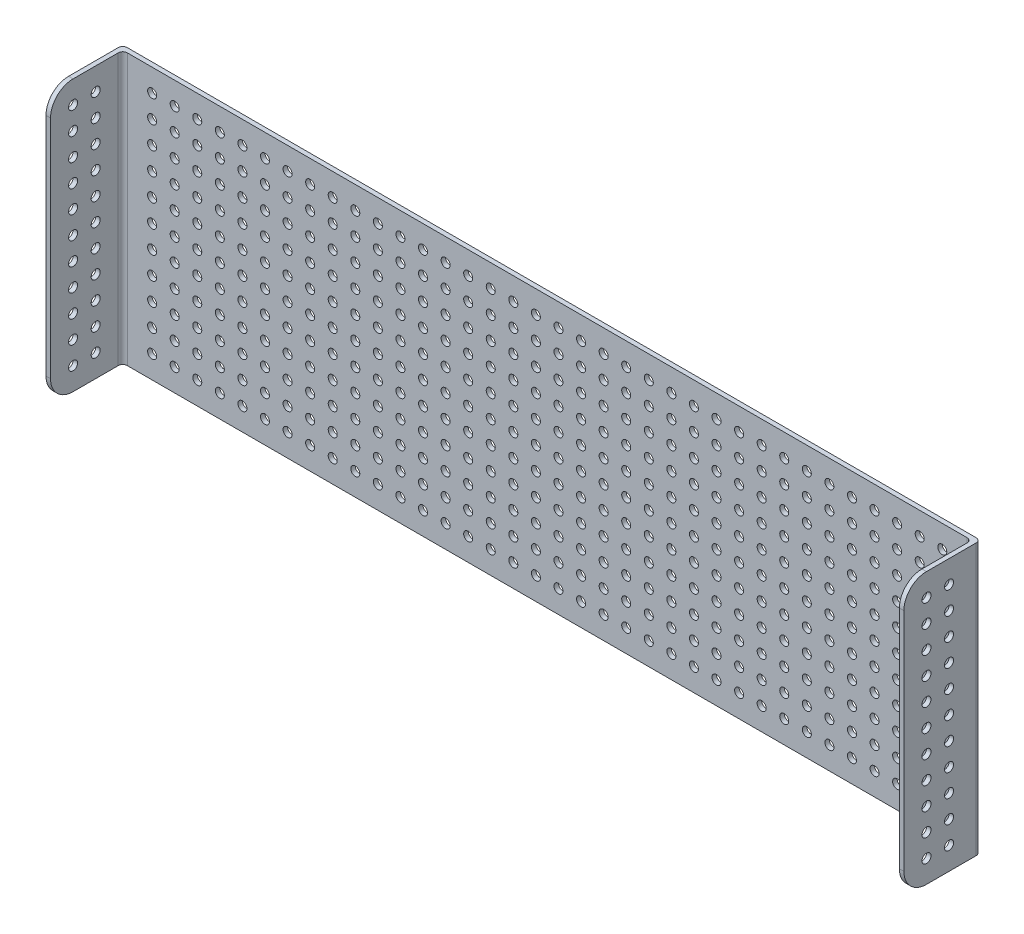
SolidWorks part; units mm, degrees
ref_plane "Front Plane" through (0, 0, 0) normal (0, 0, 1) x (1, 0, 0)
ref_plane "Top Plane" through (0, 0, 0) normal (0, 1, 0) x (1, 0, 0)
ref_plane "Right Plane" through (0, 0, 0) normal (1, 0, 0) x (0, 0, -1)
sketch "Çizim1" plane through (0, 0, 0) normal (0, 0, 1) x (1, 0, 0)
  line L1 (-65.3318, 26.6587) -> (314.6682, 26.6587)
  line L2 (-65.3318, 26.6587) -> (-65.3318, -93.3413)
  line L3 (-65.3318, -93.3413) -> (314.6682, -93.3413)
  line L4 (314.6682, 26.6587) -> (314.6682, -93.3413)
  circle A0 centre (299.6682, 16.6587) radius 2
  circle A1 centre (289.6682, 16.6587) radius 2
  circle A2 centre (279.6682, 16.6587) radius 2
  circle A3 centre (269.6682, 16.6587) radius 2
  circle A4 centre (259.6682, 16.6587) radius 2
  circle A5 centre (249.6682, 16.6587) radius 2
  circle A6 centre (239.6682, 16.6587) radius 2
  circle A7 centre (229.6682, 16.6587) radius 2
  circle A8 centre (219.6682, 16.6587) radius 2
  circle A9 centre (209.6682, 16.6587) radius 2
  circle A10 centre (199.6682, 16.6587) radius 2
  circle A11 centre (189.6682, 16.6587) radius 2
  circle A12 centre (179.6682, 16.6587) radius 2
  circle A13 centre (169.6682, 16.6587) radius 2
  circle A14 centre (159.6682, 16.6587) radius 2
  circle A15 centre (149.6682, 16.6587) radius 2
  circle A16 centre (139.6682, 16.6587) radius 2
  circle A17 centre (129.6682, 16.6587) radius 2
  circle A18 centre (119.6682, 16.6587) radius 2
  circle A19 centre (109.6682, 16.6587) radius 2
  circle A20 centre (99.6682, 16.6587) radius 2
  circle A21 centre (89.6682, 16.6587) radius 2
  circle A22 centre (79.6682, 16.6587) radius 2
  circle A23 centre (69.6682, 16.6587) radius 2
  circle A24 centre (59.6682, 16.6587) radius 2
  circle A25 centre (49.6682, 16.6587) radius 2
  circle A26 centre (39.6682, 16.6587) radius 2
  circle A27 centre (29.6682, 16.6587) radius 2
  circle A28 centre (19.6682, 16.6587) radius 2
  circle A29 centre (9.6682, 16.6587) radius 2
  circle A30 centre (-0.3318, 16.6587) radius 2
  circle A31 centre (-10.3318, 16.6587) radius 2
  circle A32 centre (-20.3318, 16.6587) radius 2
  circle A33 centre (-30.3318, 16.6587) radius 2
  circle A34 centre (-40.3318, 16.6587) radius 2
  circle A35 centre (-50.3318, 16.6587) radius 2
  circle A36 centre (289.6682, 6.6587) radius 2
  circle A37 centre (279.6682, 6.6587) radius 2
  circle A38 centre (269.6682, 6.6587) radius 2
  circle A39 centre (259.6682, 6.6587) radius 2
  circle A40 centre (249.6682, 6.6587) radius 2
  circle A41 centre (239.6682, 6.6587) radius 2
  circle A42 centre (229.6682, 6.6587) radius 2
  circle A43 centre (219.6682, 6.6587) radius 2
  circle A44 centre (209.6682, 6.6587) radius 2
  circle A45 centre (199.6682, 6.6587) radius 2
  circle A46 centre (189.6682, 6.6587) radius 2
  circle A47 centre (179.6682, 6.6587) radius 2
  circle A48 centre (169.6682, 6.6587) radius 2
  circle A49 centre (159.6682, 6.6587) radius 2
  circle A50 centre (149.6682, 6.6587) radius 2
  circle A51 centre (139.6682, 6.6587) radius 2
  circle A52 centre (129.6682, 6.6587) radius 2
  circle A53 centre (119.6682, 6.6587) radius 2
  circle A54 centre (109.6682, 6.6587) radius 2
  circle A55 centre (99.6682, 6.6587) radius 2
  circle A56 centre (89.6682, 6.6587) radius 2
  circle A57 centre (79.6682, 6.6587) radius 2
  circle A58 centre (69.6682, 6.6587) radius 2
  circle A59 centre (59.6682, 6.6587) radius 2
  circle A60 centre (49.6682, 6.6587) radius 2
  circle A61 centre (39.6682, 6.6587) radius 2
  circle A62 centre (29.6682, 6.6587) radius 2
  circle A63 centre (19.6682, 6.6587) radius 2
  circle A64 centre (9.6682, 6.6587) radius 2
  circle A65 centre (-0.3318, 6.6587) radius 2
  circle A66 centre (-10.3318, 6.6587) radius 2
  circle A67 centre (-20.3318, 6.6587) radius 2
  circle A68 centre (-30.3318, 6.6587) radius 2
  circle A69 centre (-40.3318, 6.6587) radius 2
  circle A70 centre (-50.3318, 6.6587) radius 2
  circle A71 centre (289.6682, -3.3413) radius 2
  circle A72 centre (279.6682, -3.3413) radius 2
  circle A73 centre (269.6682, -3.3413) radius 2
  circle A74 centre (259.6682, -3.3413) radius 2
  circle A75 centre (249.6682, -3.3413) radius 2
  circle A76 centre (239.6682, -3.3413) radius 2
  circle A77 centre (229.6682, -3.3413) radius 2
  circle A78 centre (219.6682, -3.3413) radius 2
  circle A79 centre (209.6682, -3.3413) radius 2
  circle A80 centre (199.6682, -3.3413) radius 2
  circle A81 centre (189.6682, -3.3413) radius 2
  circle A82 centre (179.6682, -3.3413) radius 2
  circle A83 centre (169.6682, -3.3413) radius 2
  circle A84 centre (159.6682, -3.3413) radius 2
  circle A85 centre (149.6682, -3.3413) radius 2
  circle A86 centre (139.6682, -3.3413) radius 2
  circle A87 centre (129.6682, -3.3413) radius 2
  circle A88 centre (119.6682, -3.3413) radius 2
  circle A89 centre (109.6682, -3.3413) radius 2
  circle A90 centre (99.6682, -3.3413) radius 2
  circle A91 centre (89.6682, -3.3413) radius 2
  circle A92 centre (79.6682, -3.3413) radius 2
  circle A93 centre (69.6682, -3.3413) radius 2
  circle A94 centre (59.6682, -3.3413) radius 2
  circle A95 centre (49.6682, -3.3413) radius 2
  circle A96 centre (39.6682, -3.3413) radius 2
  circle A97 centre (29.6682, -3.3413) radius 2
  circle A98 centre (19.6682, -3.3413) radius 2
  circle A99 centre (9.6682, -3.3413) radius 2
  circle A100 centre (-0.3318, -3.3413) radius 2
  circle A101 centre (-10.3318, -3.3413) radius 2
  circle A102 centre (-20.3318, -3.3413) radius 2
  circle A103 centre (-30.3318, -3.3413) radius 2
  circle A104 centre (-40.3318, -3.3413) radius 2
  circle A105 centre (-50.3318, -3.3413) radius 2
  circle A106 centre (289.6682, -13.3413) radius 2
  circle A107 centre (279.6682, -13.3413) radius 2
  circle A108 centre (269.6682, -13.3413) radius 2
  circle A109 centre (259.6682, -13.3413) radius 2
  circle A110 centre (249.6682, -13.3413) radius 2
  circle A111 centre (239.6682, -13.3413) radius 2
  circle A112 centre (229.6682, -13.3413) radius 2
  circle A113 centre (219.6682, -13.3413) radius 2
  circle A114 centre (209.6682, -13.3413) radius 2
  circle A115 centre (199.6682, -13.3413) radius 2
  circle A116 centre (189.6682, -13.3413) radius 2
  circle A117 centre (179.6682, -13.3413) radius 2
  circle A118 centre (169.6682, -13.3413) radius 2
  circle A119 centre (159.6682, -13.3413) radius 2
  circle A120 centre (149.6682, -13.3413) radius 2
  circle A121 centre (139.6682, -13.3413) radius 2
  circle A122 centre (129.6682, -13.3413) radius 2
  circle A123 centre (119.6682, -13.3413) radius 2
  circle A124 centre (109.6682, -13.3413) radius 2
  circle A125 centre (99.6682, -13.3413) radius 2
  circle A126 centre (89.6682, -13.3413) radius 2
  circle A127 centre (79.6682, -13.3413) radius 2
  circle A128 centre (69.6682, -13.3413) radius 2
  circle A129 centre (59.6682, -13.3413) radius 2
  circle A130 centre (49.6682, -13.3413) radius 2
  circle A131 centre (39.6682, -13.3413) radius 2
  circle A132 centre (29.6682, -13.3413) radius 2
  circle A133 centre (19.6682, -13.3413) radius 2
  circle A134 centre (9.6682, -13.3413) radius 2
  circle A135 centre (-0.3318, -13.3413) radius 2
  circle A136 centre (-10.3318, -13.3413) radius 2
  circle A137 centre (-20.3318, -13.3413) radius 2
  circle A138 centre (-30.3318, -13.3413) radius 2
  circle A139 centre (-40.3318, -13.3413) radius 2
  circle A140 centre (-50.3318, -13.3413) radius 2
  circle A141 centre (289.6682, -23.3413) radius 2
  circle A142 centre (279.6682, -23.3413) radius 2
  circle A143 centre (269.6682, -23.3413) radius 2
  circle A144 centre (259.6682, -23.3413) radius 2
  circle A145 centre (249.6682, -23.3413) radius 2
  circle A146 centre (239.6682, -23.3413) radius 2
  circle A147 centre (229.6682, -23.3413) radius 2
  circle A148 centre (219.6682, -23.3413) radius 2
  circle A149 centre (209.6682, -23.3413) radius 2
  circle A150 centre (199.6682, -23.3413) radius 2
  circle A151 centre (189.6682, -23.3413) radius 2
  circle A152 centre (179.6682, -23.3413) radius 2
  circle A153 centre (169.6682, -23.3413) radius 2
  circle A154 centre (159.6682, -23.3413) radius 2
  circle A155 centre (149.6682, -23.3413) radius 2
  circle A156 centre (139.6682, -23.3413) radius 2
  circle A157 centre (129.6682, -23.3413) radius 2
  circle A158 centre (119.6682, -23.3413) radius 2
  circle A159 centre (109.6682, -23.3413) radius 2
  circle A160 centre (99.6682, -23.3413) radius 2
  circle A161 centre (89.6682, -23.3413) radius 2
  circle A162 centre (79.6682, -23.3413) radius 2
  circle A163 centre (69.6682, -23.3413) radius 2
  circle A164 centre (59.6682, -23.3413) radius 2
  circle A165 centre (49.6682, -23.3413) radius 2
  circle A166 centre (39.6682, -23.3413) radius 2
  circle A167 centre (29.6682, -23.3413) radius 2
  circle A168 centre (19.6682, -23.3413) radius 2
  circle A169 centre (9.6682, -23.3413) radius 2
  circle A170 centre (-0.3318, -23.3413) radius 2
  circle A171 centre (-10.3318, -23.3413) radius 2
  circle A172 centre (-20.3318, -23.3413) radius 2
  circle A173 centre (-30.3318, -23.3413) radius 2
  circle A174 centre (-40.3318, -23.3413) radius 2
  circle A175 centre (-50.3318, -23.3413) radius 2
  circle A176 centre (289.6682, -33.3413) radius 2
  circle A177 centre (279.6682, -33.3413) radius 2
  circle A178 centre (269.6682, -33.3413) radius 2
  circle A179 centre (259.6682, -33.3413) radius 2
  circle A180 centre (249.6682, -33.3413) radius 2
  circle A181 centre (239.6682, -33.3413) radius 2
  circle A182 centre (229.6682, -33.3413) radius 2
  circle A183 centre (219.6682, -33.3413) radius 2
  circle A184 centre (209.6682, -33.3413) radius 2
  circle A185 centre (199.6682, -33.3413) radius 2
  circle A186 centre (189.6682, -33.3413) radius 2
  circle A187 centre (179.6682, -33.3413) radius 2
  circle A188 centre (169.6682, -33.3413) radius 2
  circle A189 centre (159.6682, -33.3413) radius 2
  circle A190 centre (149.6682, -33.3413) radius 2
  circle A191 centre (139.6682, -33.3413) radius 2
  circle A192 centre (129.6682, -33.3413) radius 2
  circle A193 centre (119.6682, -33.3413) radius 2
  circle A194 centre (109.6682, -33.3413) radius 2
  circle A195 centre (99.6682, -33.3413) radius 2
  circle A196 centre (89.6682, -33.3413) radius 2
  circle A197 centre (79.6682, -33.3413) radius 2
  circle A198 centre (69.6682, -33.3413) radius 2
  circle A199 centre (59.6682, -33.3413) radius 2
  circle A200 centre (49.6682, -33.3413) radius 2
  circle A201 centre (39.6682, -33.3413) radius 2
  circle A202 centre (29.6682, -33.3413) radius 2
  circle A203 centre (19.6682, -33.3413) radius 2
  circle A204 centre (9.6682, -33.3413) radius 2
  circle A205 centre (-0.3318, -33.3413) radius 2
  circle A206 centre (-10.3318, -33.3413) radius 2
  circle A207 centre (-20.3318, -33.3413) radius 2
  circle A208 centre (-30.3318, -33.3413) radius 2
  circle A209 centre (-40.3318, -33.3413) radius 2
  circle A210 centre (-50.3318, -33.3413) radius 2
  circle A211 centre (289.6682, -43.3413) radius 2
  circle A212 centre (279.6682, -43.3413) radius 2
  circle A213 centre (269.6682, -43.3413) radius 2
  circle A214 centre (259.6682, -43.3413) radius 2
  circle A215 centre (249.6682, -43.3413) radius 2
  circle A216 centre (239.6682, -43.3413) radius 2
  circle A217 centre (229.6682, -43.3413) radius 2
  circle A218 centre (219.6682, -43.3413) radius 2
  circle A219 centre (209.6682, -43.3413) radius 2
  circle A220 centre (199.6682, -43.3413) radius 2
  circle A221 centre (189.6682, -43.3413) radius 2
  circle A222 centre (179.6682, -43.3413) radius 2
  circle A223 centre (169.6682, -43.3413) radius 2
  circle A224 centre (159.6682, -43.3413) radius 2
  circle A225 centre (149.6682, -43.3413) radius 2
  circle A226 centre (139.6682, -43.3413) radius 2
  circle A227 centre (129.6682, -43.3413) radius 2
  circle A228 centre (119.6682, -43.3413) radius 2
  circle A229 centre (109.6682, -43.3413) radius 2
  circle A230 centre (99.6682, -43.3413) radius 2
  circle A231 centre (89.6682, -43.3413) radius 2
  circle A232 centre (79.6682, -43.3413) radius 2
  circle A233 centre (69.6682, -43.3413) radius 2
  circle A234 centre (59.6682, -43.3413) radius 2
  circle A235 centre (49.6682, -43.3413) radius 2
  circle A236 centre (39.6682, -43.3413) radius 2
  circle A237 centre (29.6682, -43.3413) radius 2
  circle A238 centre (19.6682, -43.3413) radius 2
  circle A239 centre (9.6682, -43.3413) radius 2
  circle A240 centre (-0.3318, -43.3413) radius 2
  circle A241 centre (-10.3318, -43.3413) radius 2
  circle A242 centre (-20.3318, -43.3413) radius 2
  circle A243 centre (-30.3318, -43.3413) radius 2
  circle A244 centre (-40.3318, -43.3413) radius 2
  circle A245 centre (-50.3318, -43.3413) radius 2
  circle A246 centre (289.6682, -53.3413) radius 2
  circle A247 centre (279.6682, -53.3413) radius 2
  circle A248 centre (269.6682, -53.3413) radius 2
  circle A249 centre (259.6682, -53.3413) radius 2
  circle A250 centre (249.6682, -53.3413) radius 2
  circle A251 centre (239.6682, -53.3413) radius 2
  circle A252 centre (229.6682, -53.3413) radius 2
  circle A253 centre (219.6682, -53.3413) radius 2
  circle A254 centre (209.6682, -53.3413) radius 2
  circle A255 centre (199.6682, -53.3413) radius 2
  circle A256 centre (189.6682, -53.3413) radius 2
  circle A257 centre (179.6682, -53.3413) radius 2
  circle A258 centre (169.6682, -53.3413) radius 2
  circle A259 centre (159.6682, -53.3413) radius 2
  circle A260 centre (149.6682, -53.3413) radius 2
  circle A261 centre (139.6682, -53.3413) radius 2
  circle A262 centre (129.6682, -53.3413) radius 2
  circle A263 centre (119.6682, -53.3413) radius 2
  circle A264 centre (109.6682, -53.3413) radius 2
  circle A265 centre (99.6682, -53.3413) radius 2
  circle A266 centre (89.6682, -53.3413) radius 2
  circle A267 centre (79.6682, -53.3413) radius 2
  circle A268 centre (69.6682, -53.3413) radius 2
  circle A269 centre (59.6682, -53.3413) radius 2
  circle A270 centre (49.6682, -53.3413) radius 2
  circle A271 centre (39.6682, -53.3413) radius 2
  circle A272 centre (29.6682, -53.3413) radius 2
  circle A273 centre (19.6682, -53.3413) radius 2
  circle A274 centre (9.6682, -53.3413) radius 2
  circle A275 centre (-0.3318, -53.3413) radius 2
  circle A276 centre (-10.3318, -53.3413) radius 2
  circle A277 centre (-20.3318, -53.3413) radius 2
  circle A278 centre (-30.3318, -53.3413) radius 2
  circle A279 centre (-40.3318, -53.3413) radius 2
  circle A280 centre (-50.3318, -53.3413) radius 2
  circle A281 centre (289.6682, -63.3413) radius 2
  circle A282 centre (279.6682, -63.3413) radius 2
  circle A283 centre (269.6682, -63.3413) radius 2
  circle A284 centre (259.6682, -63.3413) radius 2
  circle A285 centre (249.6682, -63.3413) radius 2
  circle A286 centre (239.6682, -63.3413) radius 2
  circle A287 centre (229.6682, -63.3413) radius 2
  circle A288 centre (219.6682, -63.3413) radius 2
  circle A289 centre (209.6682, -63.3413) radius 2
  circle A290 centre (199.6682, -63.3413) radius 2
  circle A291 centre (189.6682, -63.3413) radius 2
  circle A292 centre (179.6682, -63.3413) radius 2
  circle A293 centre (169.6682, -63.3413) radius 2
  circle A294 centre (159.6682, -63.3413) radius 2
  circle A295 centre (149.6682, -63.3413) radius 2
  circle A296 centre (139.6682, -63.3413) radius 2
  circle A297 centre (129.6682, -63.3413) radius 2
  circle A298 centre (119.6682, -63.3413) radius 2
  circle A299 centre (109.6682, -63.3413) radius 2
  circle A300 centre (99.6682, -63.3413) radius 2
  circle A301 centre (89.6682, -63.3413) radius 2
  circle A302 centre (79.6682, -63.3413) radius 2
  circle A303 centre (69.6682, -63.3413) radius 2
  circle A304 centre (59.6682, -63.3413) radius 2
  circle A305 centre (49.6682, -63.3413) radius 2
  circle A306 centre (39.6682, -63.3413) radius 2
  circle A307 centre (29.6682, -63.3413) radius 2
  circle A308 centre (19.6682, -63.3413) radius 2
  circle A309 centre (9.6682, -63.3413) radius 2
  circle A310 centre (-0.3318, -63.3413) radius 2
  circle A311 centre (-10.3318, -63.3413) radius 2
  circle A312 centre (-20.3318, -63.3413) radius 2
  circle A313 centre (-30.3318, -63.3413) radius 2
  circle A314 centre (-40.3318, -63.3413) radius 2
  circle A315 centre (-50.3318, -63.3413) radius 2
  circle A316 centre (289.6682, -73.3413) radius 2
  circle A317 centre (279.6682, -73.3413) radius 2
  circle A318 centre (269.6682, -73.3413) radius 2
  circle A319 centre (259.6682, -73.3413) radius 2
  circle A320 centre (249.6682, -73.3413) radius 2
  circle A321 centre (239.6682, -73.3413) radius 2
  circle A322 centre (229.6682, -73.3413) radius 2
  circle A323 centre (219.6682, -73.3413) radius 2
  circle A324 centre (209.6682, -73.3413) radius 2
  circle A325 centre (199.6682, -73.3413) radius 2
  circle A326 centre (189.6682, -73.3413) radius 2
  circle A327 centre (179.6682, -73.3413) radius 2
  circle A328 centre (169.6682, -73.3413) radius 2
  circle A329 centre (159.6682, -73.3413) radius 2
  circle A330 centre (149.6682, -73.3413) radius 2
  circle A331 centre (139.6682, -73.3413) radius 2
  circle A332 centre (129.6682, -73.3413) radius 2
  circle A333 centre (119.6682, -73.3413) radius 2
  circle A334 centre (109.6682, -73.3413) radius 2
  circle A335 centre (99.6682, -73.3413) radius 2
  circle A336 centre (89.6682, -73.3413) radius 2
  circle A337 centre (79.6682, -73.3413) radius 2
  circle A338 centre (69.6682, -73.3413) radius 2
  circle A339 centre (59.6682, -73.3413) radius 2
  circle A340 centre (49.6682, -73.3413) radius 2
  circle A341 centre (39.6682, -73.3413) radius 2
  circle A342 centre (29.6682, -73.3413) radius 2
  circle A343 centre (19.6682, -73.3413) radius 2
  circle A344 centre (9.6682, -73.3413) radius 2
  circle A345 centre (-0.3318, -73.3413) radius 2
  circle A346 centre (-10.3318, -73.3413) radius 2
  circle A347 centre (-20.3318, -73.3413) radius 2
  circle A348 centre (-30.3318, -73.3413) radius 2
  circle A349 centre (-40.3318, -73.3413) radius 2
  circle A350 centre (-50.3318, -73.3413) radius 2
  circle A351 centre (289.6682, -83.3413) radius 2
  circle A352 centre (279.6682, -83.3413) radius 2
  circle A353 centre (269.6682, -83.3413) radius 2
  circle A354 centre (259.6682, -83.3413) radius 2
  circle A355 centre (249.6682, -83.3413) radius 2
  circle A356 centre (239.6682, -83.3413) radius 2
  circle A357 centre (229.6682, -83.3413) radius 2
  circle A358 centre (219.6682, -83.3413) radius 2
  circle A359 centre (209.6682, -83.3413) radius 2
  circle A360 centre (199.6682, -83.3413) radius 2
  circle A361 centre (189.6682, -83.3413) radius 2
  circle A362 centre (179.6682, -83.3413) radius 2
  circle A363 centre (169.6682, -83.3413) radius 2
  circle A364 centre (159.6682, -83.3413) radius 2
  circle A365 centre (149.6682, -83.3413) radius 2
  circle A366 centre (139.6682, -83.3413) radius 2
  circle A367 centre (129.6682, -83.3413) radius 2
  circle A368 centre (119.6682, -83.3413) radius 2
  circle A369 centre (109.6682, -83.3413) radius 2
  circle A370 centre (99.6682, -83.3413) radius 2
  circle A371 centre (89.6682, -83.3413) radius 2
  circle A372 centre (79.6682, -83.3413) radius 2
  circle A373 centre (69.6682, -83.3413) radius 2
  circle A374 centre (59.6682, -83.3413) radius 2
  circle A375 centre (49.6682, -83.3413) radius 2
  circle A376 centre (39.6682, -83.3413) radius 2
  circle A377 centre (29.6682, -83.3413) radius 2
  circle A378 centre (19.6682, -83.3413) radius 2
  circle A379 centre (9.6682, -83.3413) radius 2
  circle A380 centre (-0.3318, -83.3413) radius 2
  circle A381 centre (-10.3318, -83.3413) radius 2
  circle A382 centre (-20.3318, -83.3413) radius 2
  circle A383 centre (-30.3318, -83.3413) radius 2
  circle A384 centre (-40.3318, -83.3413) radius 2
  circle A385 centre (-50.3318, -83.3413) radius 2
  circle A386 centre (299.6682, 6.6587) radius 2
  circle A387 centre (299.6682, -3.3413) radius 2
  circle A388 centre (299.6682, -13.3413) radius 2
  circle A389 centre (299.6682, -23.3413) radius 2
  circle A390 centre (299.6682, -33.3413) radius 2
  circle A391 centre (299.6682, -43.3413) radius 2
  circle A392 centre (299.6682, -53.3413) radius 2
  circle A393 centre (299.6682, -63.3413) radius 2
  circle A394 centre (299.6682, -73.3413) radius 2
  circle A395 centre (299.6682, -83.3413) radius 2
  dimension "D3" = 4
  dimension "D1" = 380
  dimension "D2" = 120
  dimension "D4" = 10
  dimension "D5" = 15
  dimension "D6" = 36
  dimension "D7" = 11
extrude "Boss-Extrude1" add sketch "Çizim1" along normal blind 2
sketch "Çizim3" plane through (0, 0, 2) normal (0, 0, 1) x (1, 0, 0)
  line L0 (-65.3318, -93.3413) -> (314.6682, -93.3413) construction
  line L1 (-65.3318, 26.6587) -> (-63.3318, 26.6587)
  line L2 (-65.3318, 26.6587) -> (-65.3318, -93.3413)
  line L3 (-65.3318, -93.3413) -> (-63.3318, -93.3413)
  line L4 (-63.3318, 26.6587) -> (-63.3318, -93.3413)
  line L5 (314.6682, 26.6587) -> (-65.3318, 26.6587) construction
  line L6 (312.6682, 26.6587) -> (314.6682, 26.6587)
  line L7 (312.6682, 26.6587) -> (312.6682, -93.3413)
  line L8 (312.6682, -93.3413) -> (314.6682, -93.3413)
  line L9 (314.6682, 26.6587) -> (314.6682, -93.3413)
  dimension "D1" = 2
  dimension "D2" = 2
extrude "Top Holes" add sketch "Çizim3" along normal blind 32
sketch "Çizim4" plane through (-65.3318, 0, 0) normal (-1, 0, 0) x (0, 0, 1)
  line L0 (34, -93.3413) -> (0, -93.3413) construction
  line L1 (34, 26.6587) -> (34, -93.3413) construction
  circle A0 centre (14, -83.3413) radius 2
  circle A1 centre (24, -83.3413) radius 2
  circle A2 centre (24, -73.3413) radius 2
  circle A3 centre (24, -63.3413) radius 2
  circle A4 centre (24, -53.3413) radius 2
  circle A5 centre (24, -43.3413) radius 2
  circle A6 centre (24, -33.3413) radius 2
  circle A7 centre (24, -23.3413) radius 2
  circle A8 centre (24, -13.3413) radius 2
  circle A9 centre (24, -3.3413) radius 2
  circle A10 centre (24, 6.6587) radius 2
  circle A11 centre (24, 16.6587) radius 2
  circle A12 centre (14, -73.3413) radius 2
  circle A13 centre (14, -63.3413) radius 2
  circle A14 centre (14, -53.3413) radius 2
  circle A15 centre (14, -43.3413) radius 2
  circle A16 centre (14, -33.3413) radius 2
  circle A17 centre (14, -23.3413) radius 2
  circle A18 centre (14, -13.3413) radius 2
  circle A19 centre (14, -3.3413) radius 2
  circle A20 centre (14, 6.6587) radius 2
  circle A21 centre (14, 16.6587) radius 2
  dimension "D1" = 4
  dimension "D2" = 10
  dimension "D5" = 10
  dimension "D3" = 2
  dimension "D4" = 11
extrude "Cut-Extrude1" cut sketch "Çizim4" against normal through all
fillet "Fillet1" radius 2 4 edges at (-63.3318, -33.3413, 2) (314.6682, -33.3413, 0) (312.6682, -33.3413, 2) (-65.3318, -33.3413, 0)
fillet "Fillet2" radius 10 4 edges at (-64.3318, -93.3413, 34) (-64.3318, 26.6587, 34) (313.6682, 26.6587, 34) (313.6682, -93.3413, 34)
